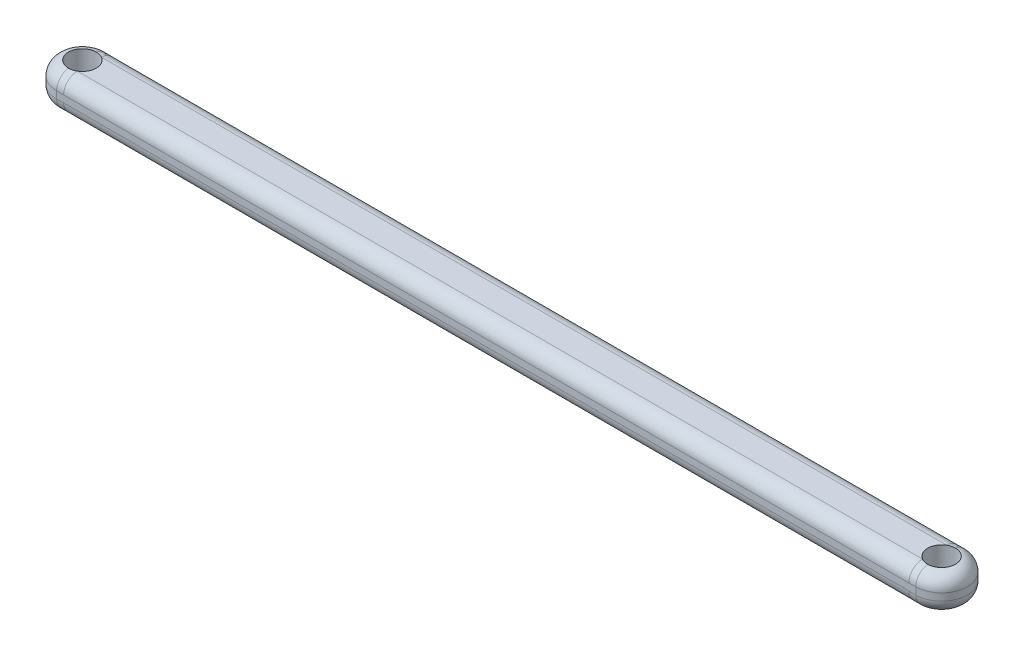
SolidWorks part; units mm, degrees
material "ABS PC"
ref_plane "Alzado" through (0, 0, 0) normal (1, 0, 0) x (0, 1, 0)
ref_plane "Planta" through (0, 0, 0) normal (0, 0, 1) x (0, 1, 0)
ref_plane "Vista lateral" through (0, 0, 0) normal (0, 1, 0) x (-1, 0, 0)
sketch "Croquis1" plane through (0, 0, 0) normal (0, 1, 0) x (-1, 0, 0)
  line L0 (0, 0) -> (250, 0) construction
  line L6 (0, -7.5) -> (250, -7.5)
  line L8 (250, 7.5) -> (0, 7.5)
  line L9 (125, -7.5) -> (125, 0) construction
  circle A0 centre (0, 0) radius 4.05
  circle A1 centre (250, 0) radius 4.05
  circle A2 centre (0, 0) radius 10 construction
  arc A3 (250, -7.5) -> (257.5, 0) centre (250, 0) ccw construction
  circle A8 centre (250, 0) radius 10 construction
  arc A9 (250, -7.5) -> (257.5, 0) centre (250, 0) ccw construction
  arc A10 (250, -7.5) -> (250, 7.5) centre (250, 0) ccw
  arc A12 (0, -7.5) -> (0, 7.5) centre (0, 0) cw
  point P8 (0, 0)
  dimension "D3" = 8.1
  dimension "D4" = 20
  dimension "D1" = 250
  dimension "D2" = 15
extrude "Saliente-Extruir1" add sketch "Croquis1" along normal mid plane 10
fillet "Redondeo6" radius 4 8 edges at (-257.5, 5, 0) (-257.5, -5, 0) (-125, 5, 7.5) (-125, -5, 7.5) (7.5, 5, 0) (7.5, -5, 0) (-125, 5, -7.5) (-125, -5, -7.5)
sketch "Croquis2" plane through (0, -5, 0) normal (0, 1, 0) x (-1, 0, 0)
  circle A0 centre (0, 0) radius 6.2
  circle A1 centre (250, 0) radius 6.2
  dimension "D1" = 12.4
extrude "Cortar-Extruir1" [suppressed] cut sketch "Croquis2" along normal blind 1.2
equation "\"L1\"= 250"
equation "\"ancho\"= 15"
equation "\"esp\"= 10"
equation "\"agujeros\"=8.1"
equation "\"D1@Croquis1\"=\"L1\""
equation "\"D2@Croquis1\"=\"ancho\""
equation "\"D3@Croquis1\"=\"agujeros\""
equation "\"D1@Saliente-Extruir1\"=\"esp\""
